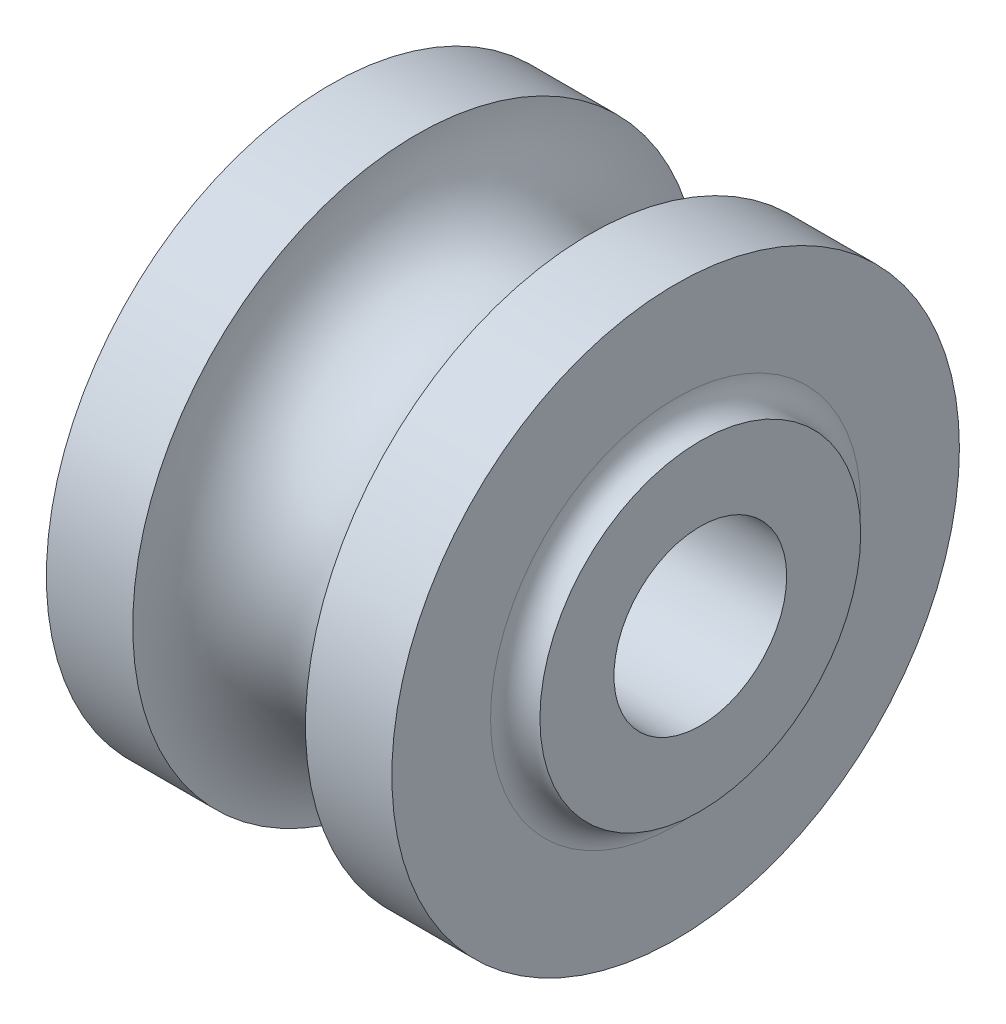
SolidWorks part; units mm, degrees
ref_plane "Front Plane" through (0, 0, 0) normal (0, 0, 1) x (1, 0, 0)
ref_plane "Top Plane" through (0, 0, 0) normal (0, 1, 0) x (1, 0, 0)
ref_plane "Right Plane" through (0, 0, 0) normal (1, 0, 0) x (0, 0, -1)
sketch "Sketch1" plane through (0, 0, 0) normal (0, 0, 1) x (1, 0, 0)
  line L0 (-16, 7) -> (16, 7)
  line L1 (16, 7) -> (16, 13)
  line L2 (16, 13) -> (14, 13)
  line L3 (14, 13) -> (14, 23)
  line L4 (14, 23) -> (7, 23)
  line L5 (0, 23) -> (0, 7) construction
  line L6 (-14, 13) -> (-14, 23)
  line L7 (-16, 13) -> (-14, 13)
  line L8 (-16, 7) -> (-16, 13)
  line L9 (-7, 23) -> (-14, 23)
  line L10 (0, 0) -> (-19.7066, 0) construction
  arc A0 (7, 23) -> (-7, 23) centre (0, 23) cw
  dimension "D6" = 7
  dimension "D1" = 16
  dimension "D2" = 13
  dimension "D3" = 7
  dimension "D4" = 23
  dimension "D5" = 2
revolve "Revolve1" add sketch "Sketch1" angle 360 about L10
fillet "Fillet1" radius 2 2 edges at (14, 0, -13) (-14, 0, -13)
